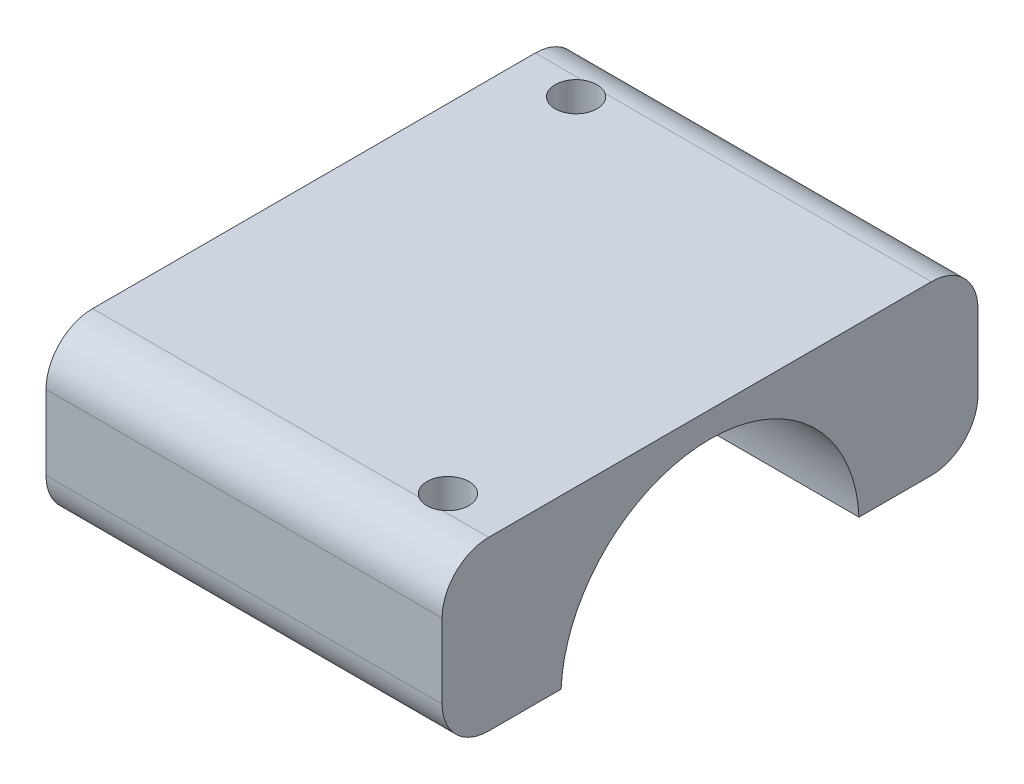
SolidWorks part; units mm, degrees
ref_plane "Front Plane" through (0, 0, 0) normal (0, 0, 1) x (1, 0, 0)
ref_plane "Top Plane" through (0, 0, 0) normal (0, 1, 0) x (1, 0, 0)
ref_plane "Right Plane" through (0, 0, 0) normal (1, 0, 0) x (0, 0, -1)
sketch "Sketch1" plane through (0, 0, 0) normal (1, 0, 0) x (0, 0, -1)
  line L0 (-19, 0.6) -> (19, 0.6)
  line L1 (23, 4.6) -> (23, 10.999)
  line L2 (19, 14.999) -> (-19, 14.999)
  line L3 (-23, 10.999) -> (-23, 4.6)
  arc A0 (19, 0.6) -> (23, 4.6) centre (19, 4.6) ccw
  arc A1 (23, 10.999) -> (19, 14.999) centre (19, 10.999) ccw
  arc A2 (-19, 14.999) -> (-23, 10.999) centre (-19, 10.999) ccw
  arc A3 (-23, 4.6) -> (-19, 0.6) centre (-19, 4.6) ccw
extrude "Boss-Extrude1" add sketch "Sketch1" along normal mid plane 34
sketch "Sketch2" plane through (0, 0, 0) normal (1, 0, 0) x (0, 0, -1)
  circle A0 centre (0, 0) radius 12.8
extrude "Cut-Extrude1" cut sketch "Sketch2" against normal through all and the other way through all
ref_plane "Plane1" through (0, 0.6, 0) normal (0, 1, 0) x (1, 0, 0)
sketch "Sketch3" plane through (0, 0.6, 0) normal (0, 1, 0) x (1, 0, 0)
  circle A0 centre (12, -17.5) radius 1.8
  circle A1 centre (-12, 17.5) radius 1.8
extrude "Cut-Extrude2" cut sketch "Sketch3" along normal blind 14.999
